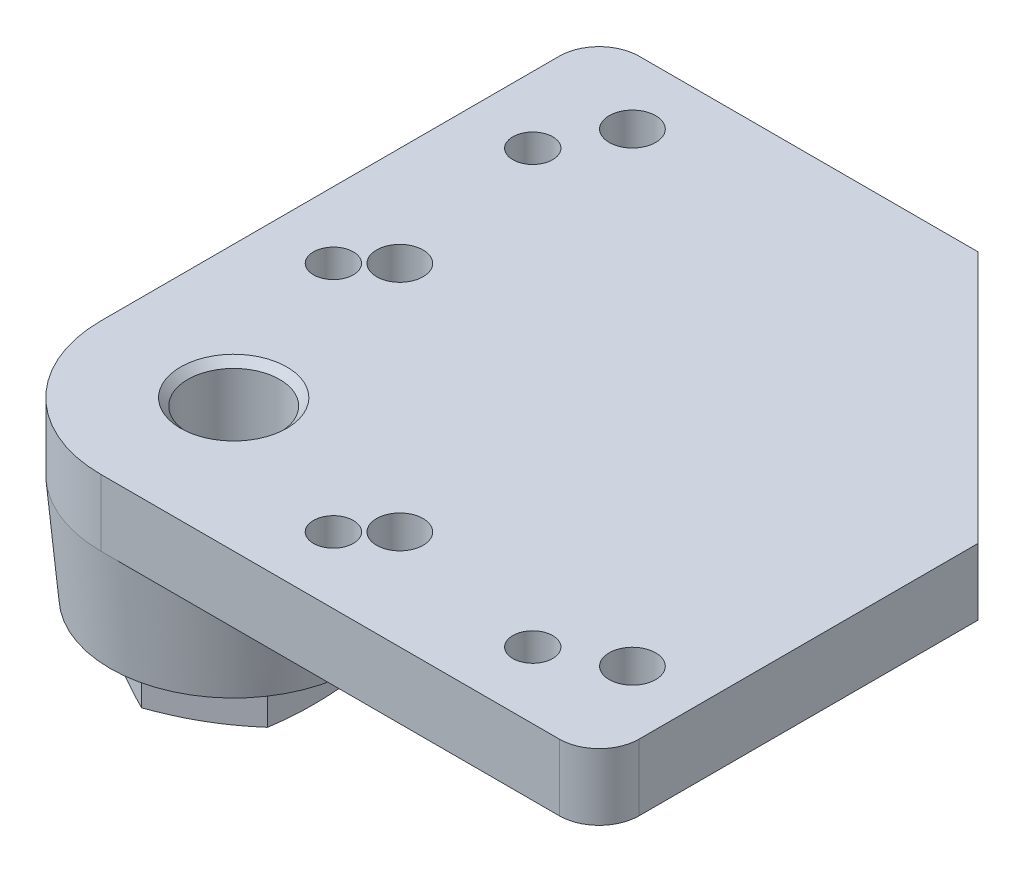
SolidWorks part; units mm, degrees
material "A6061"
ref_plane "前视基准面" through (0, 0, 0) normal (0, 0, 1) x (1, 0, 0)
ref_plane "上视基准面" through (0, 0, 0) normal (0, 1, 0) x (1, 0, 0)
ref_plane "右视基准面" through (0, 0, 0) normal (1, 0, 0) x (0, 0, -1)
sketch "草图1" plane through (0, 0, 0) normal (0, 1, 0) x (1, 0, 0)
  line L0 (0, -20) -> (69, -20)
  line L1 (75, -14) -> (75, 37)
  line L2 (75, 37) -> (37, 75)
  line L3 (37, 75) -> (-14, 75)
  line L4 (-20, 69) -> (-20, 0)
  arc A0 (-20, 0) -> (0, -20) centre (0, 0) ccw
  arc A1 (69, -20) -> (75, -14) centre (69, -14) ccw
  arc A2 (-14, 75) -> (-20, 69) centre (-14, 69) ccw
  circle A3 centre (65, -5) radius 3.5
  circle A4 centre (55, -10) radius 3
  circle A5 centre (30, -5) radius 3.5
  circle A6 centre (25, -10) radius 3
  circle A7 centre (-5, 30) radius 3.5
  circle A8 centre (-5, 65) radius 3.5
  circle A9 centre (-10, 25) radius 3
  circle A10 centre (-10, 55) radius 3
extrude "凸台-拉伸1" add sketch "草图1" against normal blind 10
ref_plane "基准面1" through (0, -10, 0) normal (0, 1, 0) x (1, 0, 0)
sketch "草图2" plane through (0, -10, 0) normal (0, 1, 0) x (1, 0, 0)
  circle A0 centre (0, 0) radius 20
extrude "凸台-拉伸2" add sketch "草图2" against normal blind 16 draft 5
sketch "草图3" plane through (0, 0, 0) normal (0, 0, 1) x (1, 0, 0)
  line L0 (0, -26) -> (12, -26)
  line L1 (12, -26) -> (14.4, -26.6431)
  line L2 (14.4, -26.6431) -> (14.4, -33.3569)
  line L3 (14.4, -33.3569) -> (12, -34)
  line L4 (12, -34) -> (0, -34)
  line L5 (0, -34) -> (0, -26)
  line L6 (0, -34) -> (0, -26) construction
revolve "旋转1" add sketch "草图3" angle 360 about L6 reverse direction yes
ref_plane "基准面2" through (0, -26, 0) normal (0, 1, 0) x (1, 0, 0)
sketch "草图4" plane through (0, -26, 0) normal (0, 1, 0) x (1, 0, 0)
  line L0 (-24, -24) -> (24, -24)
  line L1 (24, -24) -> (24, 24)
  line L2 (24, 24) -> (-24, 24)
  line L3 (-24, 24) -> (-24, -24)
  line L4 (-12, -6.9282) -> (0, -13.8564)
  line L5 (0, -13.8564) -> (12, -6.9282)
  line L6 (12, -6.9282) -> (12, 6.9282)
  line L7 (12, 6.9282) -> (0, 13.8564)
  line L8 (0, 13.8564) -> (-12, 6.9282)
  line L9 (-12, 6.9282) -> (-12, -6.9282)
extrude "切除-拉伸1" cut sketch "草图4" against normal blind 16
ref_plane "基准面3" through (-10, 0, 0) normal (1, 0, 0) x (0, 0, -1)
sketch "草图5" plane through (0, 0, 0) normal (0, 0, 1) x (1, 0, 0)
  line L0 (0, 0) -> (8, 0)
  line L1 (8, 0) -> (6.9175, -1.0825)
  line L2 (6.9175, -1.0825) -> (6.9175, -32.9175)
  line L3 (6.9175, -32.9175) -> (8, -34)
  line L4 (8, -34) -> (0, -34)
  line L5 (0, -34) -> (0, 0)
  line L6 (0, -34) -> (0, 0) construction
revolve "切除-旋转1" cut sketch "草图5" angle 360 about L6 reverse direction yes
cosmetic thread "装饰螺纹线1" parameters "D1"=34, "D2"=16
sketch "草图6" plane through (0, -10, 0) normal (0, 1, 0) x (1, 0, 0)
  line L0 (6.574, 34.574) -> (34.574, 6.574)
  line L1 (41.645, 6.574) -> (69.9293, 34.8582)
  line L2 (69.9293, 41.9293) -> (41.9293, 69.9293)
  line L3 (34.8582, 69.9293) -> (6.574, 41.645)
  arc A0 (6.574, 41.645) -> (6.574, 34.574) centre (10.1095, 38.1095) ccw
  arc A1 (34.574, 6.574) -> (41.645, 6.574) centre (38.1095, 10.1095) ccw
  arc A2 (69.9293, 34.8582) -> (69.9293, 41.9293) centre (66.3938, 38.3938) ccw
  arc A3 (41.9293, 69.9293) -> (34.8582, 69.9293) centre (38.3938, 66.3938) ccw
ref_plane "基准面4" through (0, 0, 0) normal (0.7071, 0, 0.7071) x (0.7071, 0, -0.7071)
sketch "草图7" plane through (0, 0, 0) normal (0.7071, 0, 0.7071) x (0.7071, 0, -0.7071)
  line L0 (55, -12) -> (75, -12)
  line L1 (75, -12) -> (72.5858, -14.4142)
  line L2 (71.1716, -15) -> (55, -15)
  line L3 (55, -15) -> (55, -12)
  line L4 (55, -15) -> (55, -12) construction
  arc A0 (72.5858, -14.4142) -> (71.1716, -15) centre (71.1716, -13) cw
extrude "凸台-拉伸3" add sketch "草图6" against normal blind 2 draft 10
revolve "旋转2" add sketch "草图7" angle 360 about L4 reverse direction yes
ref_plane "基准面5" through (0, -15, 0) normal (0, 1, 0) x (1, 0, 0)
ref_plane "基准面6" through (0, -10, 0) normal (0, 1, 0) x (1, 0, 0)
ref_plane "基准面7" through (0, 2, 0) normal (0, 1, 0) x (1, 0, 0)
ref_plane "bolt_5_60 1 XY" through (0, -10, 0) normal (0, 1, 0) x (1, 0, 0)
ref_plane "bolt_5_60 1 XZ" through (0, 0, -55) normal (0, 0, 1) x (1, 0, 0)
ref_plane "bolt_5_60 1 YZ" through (-10, 0, 0) normal (1, 0, 0) x (0, 0, -1)
ref_axis "bolt_5_60 1 X" through (-80.9, -10, -55) along (1, 0, 0)
ref_axis "bolt_5_60 1 Y" through (-10, -10, 50) along (0, 0, -1)
ref_axis "bolt_5_60 1 Z" through (-10, 50, -55) along (0, -1, 0)
sketch3d "bolt_5_60 1"
  point P0 (-10, -10, -55)
ref_plane "bolt_5_60 2 XY" through (0, -10, 0) normal (0, 1, 0) x (1, 0, 0)
ref_plane "bolt_5_60 2 XZ" through (0, 0, -25) normal (0, 0, 1) x (1, 0, 0)
ref_plane "bolt_5_60 2 YZ" through (-10, 0, 0) normal (1, 0, 0) x (0, 0, -1)
ref_axis "bolt_5_60 2 X" through (-80.9, -10, -25) along (1, 0, 0)
ref_axis "bolt_5_60 2 Y" through (-10, -10, 50) along (0, 0, -1)
ref_axis "bolt_5_60 2 Z" through (-10, 50, -25) along (0, -1, 0)
sketch3d "bolt_5_60 2"
  point P0 (-10, -10, -25)
ref_plane "bolt_5_60 3 XY" through (0, -10, 0) normal (0, 1, 0) x (1, 0, 0)
ref_plane "bolt_5_60 3 XZ" through (0, 0, 10) normal (0, 0, 1) x (1, 0, 0)
ref_plane "bolt_5_60 3 YZ" through (25, 0, 0) normal (1, 0, 0) x (0, 0, -1)
ref_axis "bolt_5_60 3 X" through (-80.9, -10, 10) along (1, 0, 0)
ref_axis "bolt_5_60 3 Y" through (25, -10, 50) along (0, 0, -1)
ref_axis "bolt_5_60 3 Z" through (25, 50, 10) along (0, -1, 0)
sketch3d "bolt_5_60 3"
  point P0 (25, -10, 10)
ref_plane "bolt_5_60 4 XY" through (0, -10, 0) normal (0, 1, 0) x (1, 0, 0)
ref_plane "bolt_5_60 4 XZ" through (0, 0, 10) normal (0, 0, 1) x (1, 0, 0)
ref_plane "bolt_5_60 4 YZ" through (55, 0, 0) normal (1, 0, 0) x (0, 0, -1)
ref_axis "bolt_5_60 4 X" through (-80.9, -10, 10) along (1, 0, 0)
ref_axis "bolt_5_60 4 Y" through (55, -10, 50) along (0, 0, -1)
ref_axis "bolt_5_60 4 Z" through (55, 50, 10) along (0, -1, 0)
sketch3d "bolt_5_60 4"
  point P0 (55, -10, 10)
ref_plane "bolt_6_60 1 XY" through (0, -10, 0) normal (0, 1, 0) x (1, 0, 0)
ref_plane "bolt_6_60 1 XZ" through (0, 0, -65) normal (0, 0, 1) x (1, 0, 0)
ref_plane "bolt_6_60 1 YZ" through (-5, 0, 0) normal (1, 0, 0) x (0, 0, -1)
ref_axis "bolt_6_60 1 X" through (-80.9, -10, -65) along (1, 0, 0)
ref_axis "bolt_6_60 1 Y" through (-5, -10, 50) along (0, 0, -1)
ref_axis "bolt_6_60 1 Z" through (-5, 50, -65) along (0, -1, 0)
sketch3d "bolt_6_60 1"
  point P0 (-5, -10, -65)
ref_plane "bolt_6_60 2 XY" through (0, -10, 0) normal (0, 1, 0) x (1, 0, 0)
ref_plane "bolt_6_60 2 XZ" through (0, 0, -30) normal (0, 0, 1) x (1, 0, 0)
ref_plane "bolt_6_60 2 YZ" through (-5, 0, 0) normal (1, 0, 0) x (0, 0, -1)
ref_axis "bolt_6_60 2 X" through (-80.9, -10, -30) along (1, 0, 0)
ref_axis "bolt_6_60 2 Y" through (-5, -10, 50) along (0, 0, -1)
ref_axis "bolt_6_60 2 Z" through (-5, 50, -30) along (0, -1, 0)
sketch3d "bolt_6_60 2"
  point P0 (-5, -10, -30)
ref_plane "bolt_6_60 3 XY" through (0, -10, 0) normal (0, 1, 0) x (1, 0, 0)
ref_plane "bolt_6_60 3 XZ" through (0, 0, 5) normal (0, 0, 1) x (1, 0, 0)
ref_plane "bolt_6_60 3 YZ" through (30, 0, 0) normal (1, 0, 0) x (0, 0, -1)
ref_axis "bolt_6_60 3 X" through (-80.9, -10, 5) along (1, 0, 0)
ref_axis "bolt_6_60 3 Y" through (30, -10, 50) along (0, 0, -1)
ref_axis "bolt_6_60 3 Z" through (30, 50, 5) along (0, -1, 0)
sketch3d "bolt_6_60 3"
  point P0 (30, -10, 5)
ref_plane "bolt_6_60 4 XY" through (0, -10, 0) normal (0, 1, 0) x (1, 0, 0)
ref_plane "bolt_6_60 4 XZ" through (0, 0, 5) normal (0, 0, 1) x (1, 0, 0)
ref_plane "bolt_6_60 4 YZ" through (65, 0, 0) normal (1, 0, 0) x (0, 0, -1)
ref_axis "bolt_6_60 4 X" through (-80.9, -10, 5) along (1, 0, 0)
ref_axis "bolt_6_60 4 Y" through (65, -10, 50) along (0, 0, -1)
ref_axis "bolt_6_60 4 Z" through (65, 50, 5) along (0, -1, 0)
sketch3d "bolt_6_60 4"
  point P0 (65, -10, 5)
ref_plane "nut_5_60 1 XY" through (0, 2, 0) normal (0, 1, 0) x (1, 0, 0)
ref_plane "nut_5_60 1 XZ" through (0, 0, -55) normal (0, 0, 1) x (1, 0, 0)
ref_plane "nut_5_60 1 YZ" through (-10, 0, 0) normal (1, 0, 0) x (0, 0, -1)
ref_axis "nut_5_60 1 X" through (-80.9, 2, -55) along (1, 0, 0)
ref_axis "nut_5_60 1 Y" through (-10, 2, 50) along (0, 0, -1)
ref_axis "nut_5_60 1 Z" through (-10, 50, -55) along (0, -1, 0)
sketch3d "nut_5_60 1"
  point P0 (-10, 2, -55)
ref_plane "nut_5_60 2 XY" through (0, 2, 0) normal (0, 1, 0) x (1, 0, 0)
ref_plane "nut_5_60 2 XZ" through (0, 0, -25) normal (0, 0, 1) x (1, 0, 0)
ref_plane "nut_5_60 2 YZ" through (-10, 0, 0) normal (1, 0, 0) x (0, 0, -1)
ref_axis "nut_5_60 2 X" through (-80.9, 2, -25) along (1, 0, 0)
ref_axis "nut_5_60 2 Y" through (-10, 2, 50) along (0, 0, -1)
ref_axis "nut_5_60 2 Z" through (-10, 50, -25) along (0, -1, 0)
sketch3d "nut_5_60 2"
  point P0 (-10, 2, -25)
ref_plane "nut_5_60_2 3 XY" through (0, 2, 0) normal (0, 1, 0) x (1, 0, 0)
ref_plane "nut_5_60_2 3 XZ" through (0, 0, 10) normal (0, 0, 1) x (1, 0, 0)
ref_plane "nut_5_60_2 3 YZ" through (25, 0, 0) normal (1, 0, 0) x (0, 0, -1)
ref_axis "nut_5_60_2 3 X" through (-80.9, 2, 10) along (1, 0, 0)
ref_axis "nut_5_60_2 3 Y" through (25, 2, 50) along (0, 0, -1)
ref_axis "nut_5_60_2 3 Z" through (25, 50, 10) along (0, -1, 0)
sketch3d "nut_5_60_2 3"
  point P0 (25, 2, 10)
ref_plane "nut_5_60_2 4 XY" through (0, 2, 0) normal (0, 1, 0) x (1, 0, 0)
ref_plane "nut_5_60_2 4 XZ" through (0, 0, 10) normal (0, 0, 1) x (1, 0, 0)
ref_plane "nut_5_60_2 4 YZ" through (55, 0, 0) normal (1, 0, 0) x (0, 0, -1)
ref_axis "nut_5_60_2 4 X" through (-80.9, 2, 10) along (1, 0, 0)
ref_axis "nut_5_60_2 4 Y" through (55, 2, 50) along (0, 0, -1)
ref_axis "nut_5_60_2 4 Z" through (55, 50, 10) along (0, -1, 0)
sketch3d "nut_5_60_2 4"
  point P0 (55, 2, 10)
ref_plane "nut_6_60 1 XY" through (0, 2, 0) normal (0, 1, 0) x (1, 0, 0)
ref_plane "nut_6_60 1 XZ" through (0, 0, -65) normal (0, 0, 1) x (1, 0, 0)
ref_plane "nut_6_60 1 YZ" through (-5, 0, 0) normal (1, 0, 0) x (0, 0, -1)
ref_axis "nut_6_60 1 X" through (-80.9, 2, -65) along (1, 0, 0)
ref_axis "nut_6_60 1 Y" through (-5, 2, 50) along (0, 0, -1)
ref_axis "nut_6_60 1 Z" through (-5, 50, -65) along (0, -1, 0)
sketch3d "nut_6_60 1"
  point P0 (-5, 2, -65)
ref_plane "nut_6_60 2 XY" through (0, 2, 0) normal (0, 1, 0) x (1, 0, 0)
ref_plane "nut_6_60 2 XZ" through (0, 0, -30) normal (0, 0, 1) x (1, 0, 0)
ref_plane "nut_6_60 2 YZ" through (-5, 0, 0) normal (1, 0, 0) x (0, 0, -1)
ref_axis "nut_6_60 2 X" through (-80.9, 2, -30) along (1, 0, 0)
ref_axis "nut_6_60 2 Y" through (-5, 2, 50) along (0, 0, -1)
ref_axis "nut_6_60 2 Z" through (-5, 50, -30) along (0, -1, 0)
sketch3d "nut_6_60 2"
  point P0 (-5, 2, -30)
ref_plane "nut_6_60_2 3 XY" through (0, 2, 0) normal (0, 1, 0) x (1, 0, 0)
ref_plane "nut_6_60_2 3 XZ" through (0, 0, 5) normal (0, 0, 1) x (1, 0, 0)
ref_plane "nut_6_60_2 3 YZ" through (30, 0, 0) normal (1, 0, 0) x (0, 0, -1)
ref_axis "nut_6_60_2 3 X" through (-80.9, 2, 5) along (1, 0, 0)
ref_axis "nut_6_60_2 3 Y" through (30, 2, 50) along (0, 0, -1)
ref_axis "nut_6_60_2 3 Z" through (30, 50, 5) along (0, -1, 0)
sketch3d "nut_6_60_2 3"
  point P0 (30, 2, 5)
ref_plane "nut_6_60_2 4 XY" through (0, 2, 0) normal (0, 1, 0) x (1, 0, 0)
ref_plane "nut_6_60_2 4 XZ" through (0, 0, 5) normal (0, 0, 1) x (1, 0, 0)
ref_plane "nut_6_60_2 4 YZ" through (65, 0, 0) normal (1, 0, 0) x (0, 0, -1)
ref_axis "nut_6_60_2 4 X" through (-80.9, 2, 5) along (1, 0, 0)
ref_axis "nut_6_60_2 4 Y" through (65, 2, 50) along (0, 0, -1)
ref_axis "nut_6_60_2 4 Z" through (65, 50, 5) along (0, -1, 0)
sketch3d "nut_6_60_2 4"
  point P0 (65, 2, 5)
ref_plane "to_adjuster XY" through (0, 0, 0) normal (0, 1, 0) x (1, 0, 0)
ref_plane "to_adjuster XZ" through (0, 0, 0) normal (0, 0, 1) x (1, 0, 0)
ref_plane "to_adjuster YZ" through (0, 0, 0) normal (1, 0, 0) x (0, 0, -1)
ref_axis "to_adjuster X" through (-80.9, 0, 0) along (1, 0, 0)
ref_axis "to_adjuster Y" through (0, 0, 50) along (0, 0, -1)
ref_axis "to_adjuster Z" through (0, 50, 0) along (0, -1, 0)
sketch3d "to_adjuster"
  point P0 (0, 0, 0)
ref_plane "to_body XY" through (0, -15, 0) normal (0, 1, 0) x (1, 0, 0)
ref_plane "to_body XZ" through (0, 0, -38.8) normal (0, 0, 1) x (1, 0, 0)
ref_plane "to_body YZ" through (38.8, 0, 0) normal (1, 0, 0) x (0, 0, -1)
ref_axis "to_body X" through (-80.9, -15, -38.8) along (1, 0, 0)
ref_axis "to_body Y" through (38.8, -15, 50) along (0, 0, -1)
ref_axis "to_body Z" through (38.8, 50, -38.8) along (0, -1, 0)
sketch3d "to_body"
  point P0 (38.8, -15, -38.8)
ref_plane "to_dummy XY" through (0, 0, 0) normal (0, 1, 0) x (1, 0, 0)
ref_plane "to_dummy XZ" through (0, 0, 0) normal (0, 0, 1) x (1, 0, 0)
ref_plane "to_dummy YZ" through (0, 0, 0) normal (1, 0, 0) x (0, 0, -1)
ref_axis "to_dummy X" through (-80.9, 0, 0) along (1, 0, 0)
ref_axis "to_dummy Y" through (0, 0, 50) along (0, 0, -1)
ref_axis "to_dummy Z" through (0, 50, 0) along (0, -1, 0)
sketch3d "to_dummy"
  point P0 (0, 0, 0)
